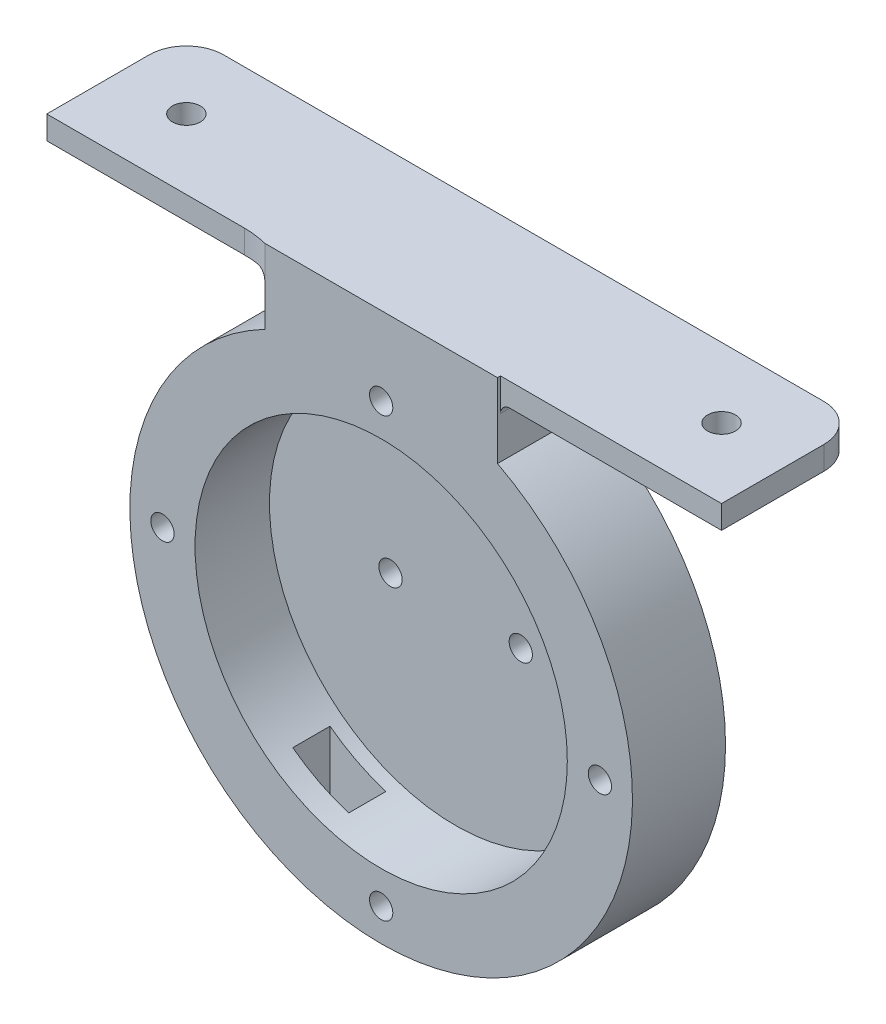
SolidWorks part; units mm, degrees
ref_plane "Front Plane" through (0, 0, 0) normal (0, 0, 1) x (1, 0, 0)
ref_plane "Top Plane" through (0, 0, 0) normal (0, 1, 0) x (1, 0, 0)
ref_plane "Right Plane" through (0, 0, 0) normal (1, 0, 0) x (0, 0, -1)
sketch "Sketch1" plane through (0, 0, 0) normal (0, 0, 1) x (1, 0, 0)
  circle A0 centre (0, 0) radius 27
  circle A1 centre (0, 0) radius 23.5 construction
  circle A2 centre (0, 23.5) radius 1.25
  circle A3 centre (23.5, 0) radius 1.25
  circle A4 centre (0, -23.5) radius 1.25
  circle A5 centre (-23.5, 0) radius 1.25
  circle A6 centre (0, 0) radius 20
  point P15 (0, 0)
  dimension "D1" = 54
  dimension "D2" = 47
  dimension "D3" = 2.5
  dimension "D5" = 40
  dimension "D4" = 4
extrude "Boss-Extrude1" add sketch "Sketch1" along normal blind 10
sketch "Sketch3" plane through (0, 0, 0) normal (0, 0, 1) x (1, 0, 0)
  circle A0 centre (0, 0) radius 20
  circle A1 centre (0, 0) radius 7 construction
  circle A2 centre (-7, 0) radius 1.25
  circle A3 centre (7, 0) radius 1.25
  circle A4 centre (0, 0) radius 11.5 construction
  dimension "D1" = 40
  dimension "D2" = 14
  dimension "D3" = 2.5
  dimension "D4" = 23
extrude "Boss-Extrude2" add sketch "Sketch3" along normal blind 2
sketch "Sketch5" plane through (0, 0, 10) normal (0, 0, 1) x (1, 0, 0)
  line L0 (0, -5.5) -> (0, 5.5) construction
  line L1 (-12.5, 23.9322) -> (-4.2519, 23.9322)
  line L2 (-12.5, 23.9322) -> (-12.5, 31.9322)
  line L3 (-12.5, 31.9322) -> (12.5, 31.9322)
  line L4 (12.5, 23.9322) -> (12.5, 31.9322)
  line L5 (4.2678, 23.9322) -> (0, 26.2545)
  line L6 (0, 26.2545) -> (-4.2519, 23.9322)
  line L7 (4.2678, 23.9322) -> (12.5, 23.9322)
  circle A0 centre (0, 0) radius 27 construction
  dimension "D1" = 12.5
  dimension "D2" = 25
  dimension "D3" = 8
extrude "Boss-Extrude3" add sketch "Sketch5" against normal blind 6
sketch "Sketch4" plane through (0, 0, 0) normal (0, 1, 0) x (1, 0, 0)
  line L0 (27, -10) -> (-27, -10) construction
  line L1 (-12, -3.5) -> (-6, -3.5)
  line L2 (-12, -3.5) -> (-12, -7.5)
  line L3 (-12, -7.5) -> (-6, -7.5)
  line L4 (-6, -3.5) -> (-6, -7.5)
  dimension "D1" = 4
  dimension "D2" = 6
  dimension "D3" = 2.5
  dimension "D4" = 6
extrude "Cut-Extrude1" cut sketch "Sketch4" against normal up to surface (26.3249 mm away) up to face at (0, 11.9661, 7)
sketch "Sketch6" plane through (0, 31.9322, 0) normal (0, 1, 0) x (1, 0, 0)
  line L0 (12.5, -4) -> (12.5, -10) construction
  line L1 (-12.5, -10) -> (12.5, -10)
  line L2 (-12.5, -10) -> (-12.5, 5.32)
  line L3 (-12.5, 5.32) -> (12.5, 5.32)
  line L4 (12.5, -10) -> (12.5, 5.32)
  dimension "D1" = 15.32
extrude "Boss-Extrude4" add sketch "Sketch6" against normal blind 2.5
sketch "Sketch7" plane through (0, 31.9322, 0) normal (0, 1, 0) x (1, 0, 0)
  line L0 (0, -8.426) -> (0, 8.426) construction
  line L1 (-36.25, -67.18) -> (36.25, -67.18) construction
  line L2 (-36.25, -67.18) -> (-36.25, 1.32) construction
  line L3 (-32.25, 5.32) -> (32.25, 5.32) construction
  line L4 (36.25, -67.18) -> (36.25, 1.32) construction
  line L5 (-28.75, -9.68) -> (-36.25, -9.68)
  line L6 (0, 5.32) -> (-36.25, 5.32)
  line L7 (-36.25, -9.68) -> (-36.25, -2.18)
  line L8 (12.5, -4) -> (-12.5, -4) construction
  line L9 (0, 5.32) -> (0, -9.68)
  line L10 (0, -9.68) -> (-28.75, -9.68)
  line L11 (-36.25, 5.32) -> (-36.25, -2.18)
  arc A0 (32.25, 5.32) -> (36.25, 1.32) centre (32.25, 1.32) cw construction
  arc A1 (-36.25, 1.32) -> (-32.25, 5.32) centre (-32.25, 1.32) cw
  circle A3 centre (-28.75, -2.18) radius 1.5
  point P4 (0, 5.32)
  point P11 (36.25, 5.32)
  point P14 (-36.25, 5.32)
  point P21 (-36.25, -9.68)
  dimension "D4" = 4
  dimension "D7" = 3
  dimension "D1" = 72.5
  dimension "D2" = 72.5
  dimension "D3" = 9.32
  dimension "D5" = 15
extrude "Boss-Extrude5" add sketch "Sketch7" against normal blind 2.5 contours L10 L9 L6 A1 L11 A3 region at (-17.8732, 31.9322, 2.2225)
fillet "Fillet2" radius 10 1 edges at (-12.5, 30.6822, 9.68)
sketch "Sketch8" plane through (0, 31.9322, 0) normal (0, 1, 0) x (1, 0, 0)
  circle A0 centre (-28.75, -2.18) radius 2.5
  circle A1 centre (-28.75, -2.18) radius 4
  dimension "D1" = 5
  dimension "D2" = 8
extrude "Boss-Extrude6" [suppressed] add sketch "Sketch8" against normal blind 5
mirror "Mirror1" about plane through (0, 0, 0) normal (1, 0, 0) of "Boss-Extrude4", "Boss-Extrude5", "Boss-Extrude6"
fillet "Fillet3" radius 1 3 edges at (0, 29.4322, 4) (12.5, 29.4322, 6.84) (-12.5, 29.4322, 7)
fillet "Fillet4" [suppressed] radius 10
